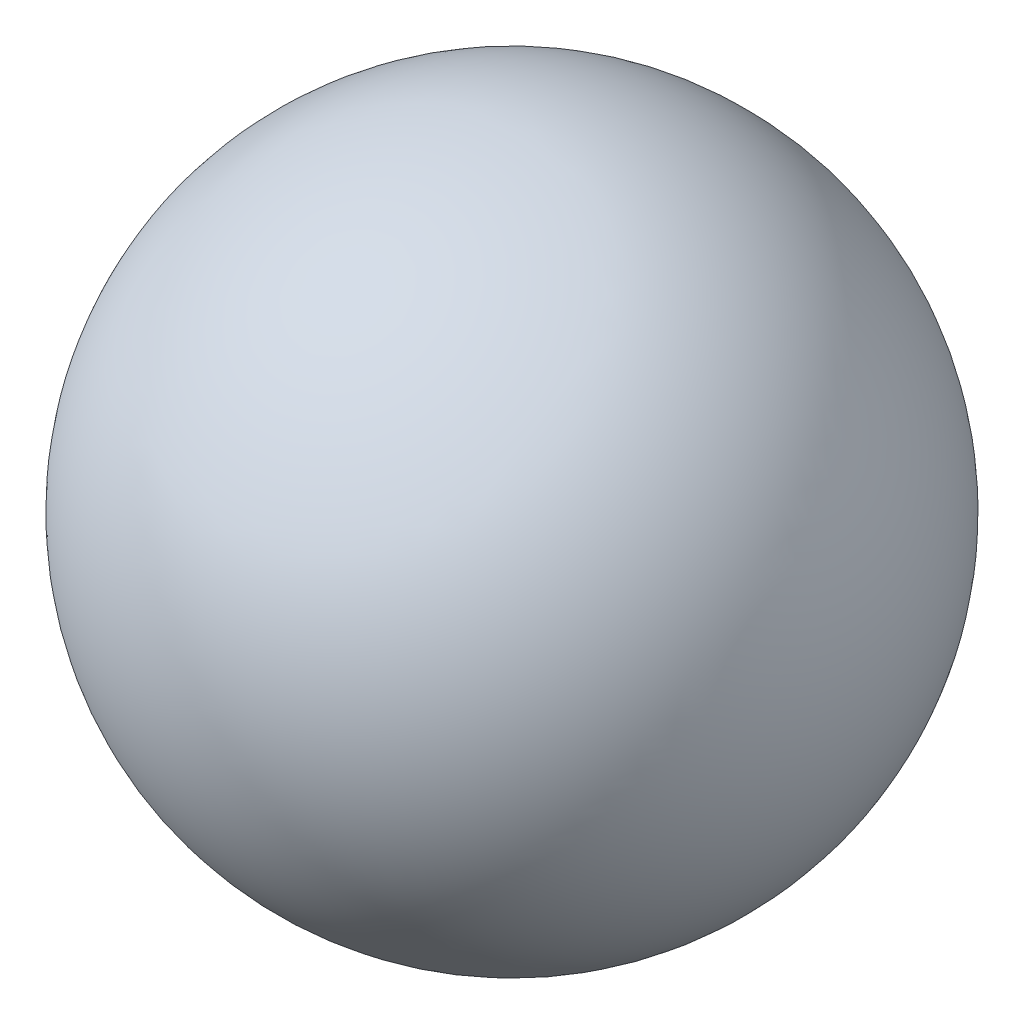
SolidWorks part; units mm, degrees
ref_plane "Front Plane" through (0, 0, 0) normal (0, 0, 1) x (1, 0, 0)
ref_plane "Top Plane" through (0, 0, 0) normal (0, 1, 0) x (1, 0, 0)
ref_plane "Right Plane" through (0, 0, 0) normal (1, 0, 0) x (0, 0, -1)
sketch "Sketch1" plane through (0, 0, 0) normal (0, 0, 1) x (1, 0, 0)
  line L0 (-1, 0) -> (1, 0) construction
  circle A0 centre (0, 0) radius 1
  dimension "D1" = 2
revolve "Revolve3" add sketch "Sketch1" angle 360 about L0 region at (0, 0.4244, 0)
